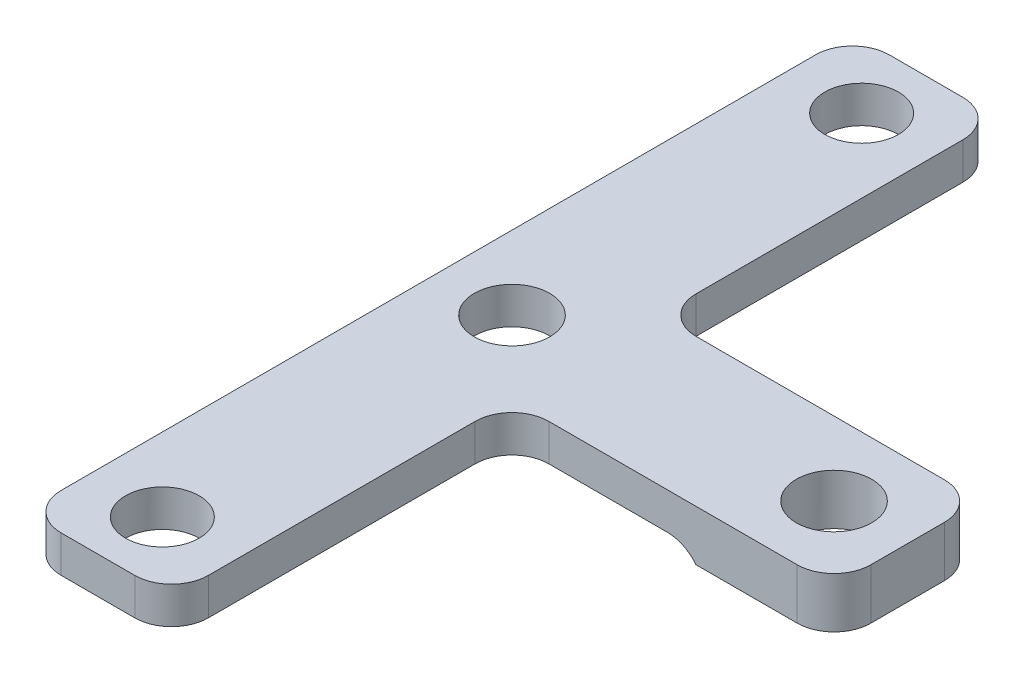
SolidWorks part; units mm, degrees
ref_plane "Front Plane" through (0, 0, 0) normal (0, 0, 1) x (1, 0, 0)
ref_plane "Top Plane" through (0, 0, 0) normal (0, 1, 0) x (1, 0, 0)
ref_plane "Right Plane" through (0, 0, 0) normal (1, 0, 0) x (0, 0, -1)
ref_axis "X-Axis" through (88.99, 0, 0) along (-1, 0, 0)
ref_axis "Y-Axis" through (0, 0, -88.99) along (0, 0, 1)
ref_axis "Z-Axis" through (0, -55, 0) along (0, 1, 0)
sketch "Sketch1" plane through (0, 0, 0) normal (0, 1, 0) x (1, 0, 0)
  line L0 (0, 88.99) -> (0, -88.99) construction
  line L2 (-8, 45) -> (-8, -45)
  line L3 (-8, -45) -> (8, -45)
  line L4 (8, 45) -> (8, 8)
  line L7 (-8, 45) -> (8, 45)
  line L9 (88.99, 0) -> (-88.99, 0) construction
  line L10 (8, 8) -> (43, 8)
  line L12 (8, -8) -> (43, -8)
  line L13 (43, 8) -> (43, -8)
  line L14 (8, -8) -> (8, -45)
  circle A0 centre (0, 0) radius 4.1
  point P4 (0, -45)
  point P7 (43, 0)
  dimension "D3" = 8.2
  dimension "D5" = 90
  dimension "D1" = 16
  dimension "D2" = 16
  dimension "D4" = 35
  dimension "D6" = 45
extrude "Boss-Extrude1" add sketch "Sketch1" along normal blind 4
sketch "Sketch2" plane through (0, 4, 0) normal (0, 1, 0) x (1, 0, 0)
  line L0 (0, 88.99) -> (0, -88.99) construction
  circle A0 centre (0, -38) radius 4
  circle A1 centre (0, 0) radius 4.1 construction
  dimension "D1" = 8
  dimension "D2" = 38
extrude "Cut-Extrude1" cut sketch "Sketch2" against normal blind 10
mirror "Mirror1" about plane through (0, 0, 0) normal (0, 0, 1) of "Cut-Extrude1"
fillet "Fillet1" radius 4 8 edges at (8, 2, -45) (-8, 2, -45) (-8, 2, 45) (43, 2, -8) (43, 2, 8) (8, 2, -8) (8, 2, 8) (8, 2, 45)
sketch "Sketch3" plane through (0, 4, 0) normal (0, 1, 0) x (1, 0, 0)
  line L0 (88.99, 0) -> (-88.99, 0) construction
  circle A0 centre (35, 0) radius 4.1
  point P2 (0, 0)
  dimension "D1" = 8.2
  dimension "D2" = 35
extrude "Cut-Extrude2" cut sketch "Sketch3" against normal blind 10
sketch "Sketch4" plane through (0, 0, 0) normal (0, 1, 0) x (1, 0, 0)
  line L0 (28, 8) -> (28, -8)
  line L8 (43, -4) -> (43, 4)
  line L9 (39, 8) -> (12, 8)
  line L10 (8, 12) -> (8, 41)
  line L11 (4, 45) -> (-4, 45)
  line L12 (-8, 41) -> (-8, -41)
  line L13 (-4, -45) -> (4, -45)
  line L14 (8, -41) -> (8, -12)
  line L15 (12, -8) -> (39, -8)
  line L16 (43, -4) -> (43, 4)
  line L17 (39, 8) -> (28, 8)
  line L21 (-4, -45) -> (4, -45)
  line L23 (28, -8) -> (39, -8)
  arc A8 (43, 4) -> (39, 8) centre (39, 4) ccw
  arc A9 (8, 12) -> (12, 8) centre (12, 12) ccw
  arc A10 (8, 41) -> (4, 45) centre (4, 41) ccw
  arc A11 (-4, 45) -> (-8, 41) centre (-4, 41) ccw
  arc A12 (-8, -41) -> (-4, -45) centre (-4, -41) ccw
  arc A13 (4, -45) -> (8, -41) centre (4, -41) ccw
  arc A14 (12, -8) -> (8, -12) centre (12, -12) ccw
  arc A15 (39, -8) -> (43, -4) centre (39, -4) ccw
  arc A16 (43, 4) -> (39, 8) centre (39, 4) ccw
  arc A23 (39, -8) -> (43, -4) centre (39, -4) ccw
  circle M55 centre (35, 0) radius 4.1
  line M58 (12, 8) -> (39, 8)
  arc M59 (39, 8) -> (43, 4) centre (39, 4) cw
  line M60 (43, 4) -> (43, -4)
  arc M61 (43, -4) -> (39, -8) centre (39, -4) cw
  line M62 (39, -8) -> (12, -8)
  dimension "D2" = 15
  dimension "D1" = 0
extrude "Boss-Extrude3" add sketch "Sketch4" against normal blind 1.5 contours L0 M58 M59 M60 M61 M62 M55 region at (33.5, 0, -7.7807)
fillet "Fillet3" radius 4 1 edges at (28, 0, 0)
